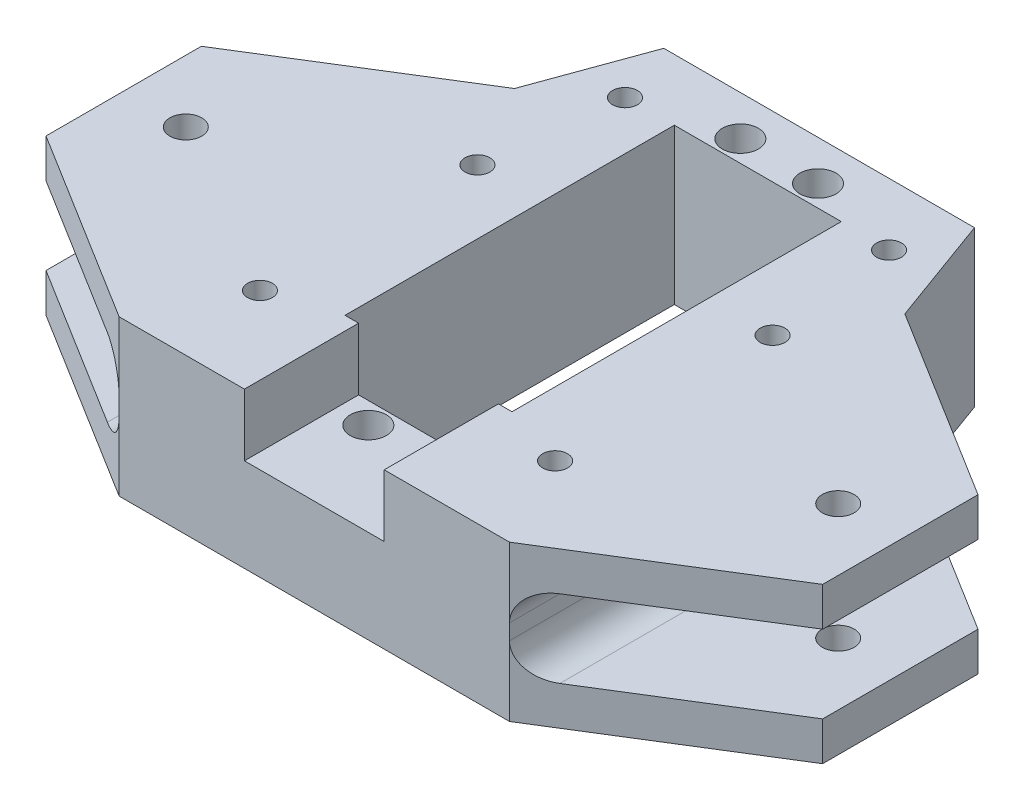
SolidWorks part; units mm, degrees
ref_plane "Front Plane" through (0, 0, 0) normal (0, 0, 1) x (1, 0, 0)
ref_plane "Top Plane" through (0, 0, 0) normal (0, 1, 0) x (1, 0, 0)
ref_plane "Right Plane" through (0, 0, 0) normal (1, 0, 0) x (0, 0, -1)
sketch "Sketch1" plane through (0, 0, 0) normal (0, 1, 0) x (1, 0, 0)
  line L0 (0, 0) -> (0, 55585.7092) construction
  line L1 (0, 0) -> (55585.7092, 0) construction
  line L2 (20, 39.5477) -> (-20, 39.5477)
  line L3 (-20, 39.5477) -> (-25.1303, 25.4523)
  line L4 (-25.1303, 25.4523) -> (-50, 10)
  line L5 (-50, 10) -> (-50, -10)
  line L11 (50, 10) -> (50, -10)
  line L12 (25.1303, 25.4523) -> (50, 10)
  line L13 (20, 39.5477) -> (25.1303, 25.4523)
  line L14 (25.1303, -25.4523) -> (50, -10)
  line L15 (-25.1303, -25.4523) -> (-50, -10)
  line L19 (25.1303, -25.4523) -> (-25.1303, -25.4523)
  point P7 (50, 0)
  point P12 (-50, 0)
  point P14 (0, -10.7407)
  point P19 (0, 39.5477)
  dimension "D1" = 40
  dimension "D2" = 20
  dimension "D3" = 65
  dimension "D4" = 100
  dimension "D5" = 110
  dimension "D8" = 15
extrude "Main-Body" add sketch "Sketch1" along normal mid plane 20
sketch "Sketch2" plane through (0, 10, 0) normal (0, 1, 0) x (1, 0, 0)
  line L0 (0, 47.5477) -> (0, -49952.4523) construction
  line L1 (-50, 0) -> (49950, 0) construction
  line L2 (20, 39.5477) -> (-20, 39.5477) construction
  line L3 (-10, 10.45) -> (10, 10.45) construction
  line L4 (10, -10) -> (-10, -10) construction
  line L5 (-10, -10) -> (-10, 30.9) construction
  line L6 (-10, 30.9) -> (10, 30.9) construction
  line L7 (10, -10) -> (10, 30.9) construction
  line L8 (0, -25.4523) -> (50000, -25.4523) construction
  line L9 (-50, 10) -> (-50, -10) construction
  line L10 (-5, 34.4) -> (5, 34.4) construction
  line L11 (-5, -13.5) -> (5, -13.5) construction
  line L12 (-25.1303, -25.4523) -> (25.1303, -25.4523) construction
  line L14 (-10.75, 31.65) -> (10.75, 31.65)
  line L15 (-10.75, 31.65) -> (-10.75, -10.75)
  line L16 (-10.75, -10.75) -> (10.75, -10.75)
  line L17 (10.75, 31.65) -> (10.75, -10.75)
  line L18 (-10.75, 31.65) -> (10.75, -10.75) construction
  line L19 (-10.75, -10.75) -> (10.75, 31.65) construction
  circle A0 centre (-5, -13.5) radius 2.325
  circle A1 centre (5, -13.5) radius 2.325
  circle A2 centre (-5, 34.4) radius 2.325
  circle A3 centre (5, 34.4) radius 2.325
  circle A4 centre (0, 0) radius 2 construction
  circle A5 centre (-42, 0) radius 2.05
  circle A6 centre (42, 0) radius 2.05
  point P22 (0, -10)
  point P23 (0, 30.9)
  point P28 (0, 39.5477)
  point P29 (0, -13.5)
  point P30 (0, 34.4)
  point P31 (-50, 0)
  point P32 (0, 10.45)
  dimension "D1" = 4.65
  dimension "D4" = 4.65
  dimension "D10" = 4.65
  dimension "D11" = 4.65
  dimension "D13" = 4
  dimension "D16" = 4.1
  dimension "D3" = 10
  dimension "D6" = 10
  dimension "D7" = 20
  dimension "D8" = 3.5
  dimension "D9" = 3.5
  dimension "D5" = 40.9
  dimension "D2" = 0.75
  dimension "D12" = 0.75
  dimension "D14" = 10
  dimension "D15" = 0
  dimension "D17" = 8
extrude "Servo&RotRod-Cutout" cut sketch "Sketch2" against normal blind 30
sketch "Sketch3" plane through (0, 0, 25.4523) normal (0, 0, 1) x (1, 0, 0)
  line L0 (0, 0) -> (0, 50000) construction
  line L1 (0, 0) -> (48695.3801, 0) construction
  line L3 (9, 10) -> (-9, 10)
  line L4 (-9, 10) -> (-9, 2)
  line L5 (-9, 2) -> (9, 2)
  line L6 (9, 10) -> (9, 2)
  line L7 (-25.1303, 10) -> (25.1303, 10) construction
  point P10 (0, 0)
  point P11 (0, 10)
  dimension "D1" = 18
  dimension "D2" = 8
  dimension "D3" = 0
extrude "Servo-Cable-Cutout" cut sketch "Sketch3" against normal up to surface (14.7023 mm away) up to face at (0, 0, 10.75)
sketch "Sketch4" plane through (0, 0, 25.4523) normal (0, 0, 1) x (1, 0, 0)
  line L0 (0, 0) -> (0, 50000) construction
  line L1 (50, 0) -> (50050, 0) construction
  line L2 (50, 10) -> (50, -10) construction
  line L3 (-50, -5) -> (-50, 5)
  line L4 (-50, 10) -> (-50, -10) construction
  line L5 (-50, 5) -> (-25.1303, 5)
  line L6 (-25.1303, 5) -> (-25.1303, -5)
  line L7 (-50, -5) -> (-25.1303, -5)
  line L10 (-25.1303, 10) -> (-25.1303, -10) construction
  point P7 (50, 0)
  point P15 (-25.1303, 0)
  point P16 (-50, 0)
  dimension "D1" = 0
  dimension "D2" = 10
extrude "Control-Arm-Cutout" cut sketch "Sketch4" against normal through all both and the other way through all
mirror "Mirror1" about plane through (0, 0, 0) normal (1, 0, 0) of "Control-Arm-Cutout"
sketch "Sketch5" plane through (0, 10, 0) normal (0, 1, 0) x (1, 0, 0)
  line L0 (-50, 0) -> (49950, 0) construction
  line L1 (-50, 10) -> (-50, -10) construction
  line L2 (0, 0) -> (0, 50000) construction
  circle A0 centre (-40, 0) radius 2.05
  point P4 (-50, 0)
  dimension "D1" = 4.1
  dimension "D2" = 10
extrude "Cut-Extrude4" [suppressed] cut sketch "Sketch5" against normal through all both and the other way through all
mirror "Mirror2" [suppressed] about plane through (0, 0, 0) normal (1, 0, 0)
fillet "Fillet1" radius 4 4 edges at (-25.1303, -5, 0) (-25.1303, 5, 0) (25.1303, -5, 0) (25.1303, 5, 0)
sketch "Sketch6" plane through (0, -10, 0) normal (0, -1, 0) x (1, 0, 0)
  line L0 (0, 0) -> (0, -50000) construction
  line L1 (19, -12.4414) -> (19, -50012.4414) construction
  line L2 (-25.1303, 25.4523) -> (25.1303, 25.4523) construction
  line L3 (20, -39.5477) -> (-20, -39.5477) construction
  circle A0 centre (19, -14.5477) radius 1.6
  circle A1 centre (19, 13.4523) radius 1.6
  circle A2 centre (17, -31.5477) radius 1.6
  circle A3 centre (-17, -31.5477) radius 1.6
  circle A4 centre (-19, 13.4523) radius 1.6
  circle A5 centre (-19, -14.5477) radius 1.6
  dimension "D2" = 3.2
  dimension "D3" = 3.2
  dimension "D7" = 3.2
  dimension "D1" = 19
  dimension "D4" = 12
  dimension "D5" = 25
  dimension "D6" = 17
  dimension "D8" = 8
extrude "Mount-Holes-Chassis" cut sketch "Sketch6" against normal through all
sketch "Sketch7" plane through (0, -10, 0) normal (0, -1, 0) x (1, 0, 0)
  line L0 (0, 0) -> (0, -50000) construction
  circle A0 centre (17, -31.5477) radius 3.25
  circle A1 centre (19, -14.5477) radius 3.25
  circle A2 centre (19, 13.4523) radius 3.25
  circle A3 centre (-19, 13.4523) radius 3.25
  circle A4 centre (-19, -14.5477) radius 3.25
  circle A5 centre (-17, -31.5477) radius 3.25
  dimension "D1" = 6.5
  dimension "D2" = 6.5
  dimension "D3" = 6.5
extrude "Bolt-Head-Holes" cut sketch "Sketch7" against normal blind 4.5
equation "\"D10@Sketch2\"=\"D1@Sketch2\""
equation "\"D11@Sketch2\"=\"D1@Sketch2\""
equation "\"D3@Sketch6\"=\"D2@Sketch6\""
equation "\"D7@Sketch6\"=\"D2@Sketch6\""
equation "\"D2@Sketch7\"=\"D1@Sketch7\""
equation "\"D3@Sketch7\"=\"D1@Sketch7\""
